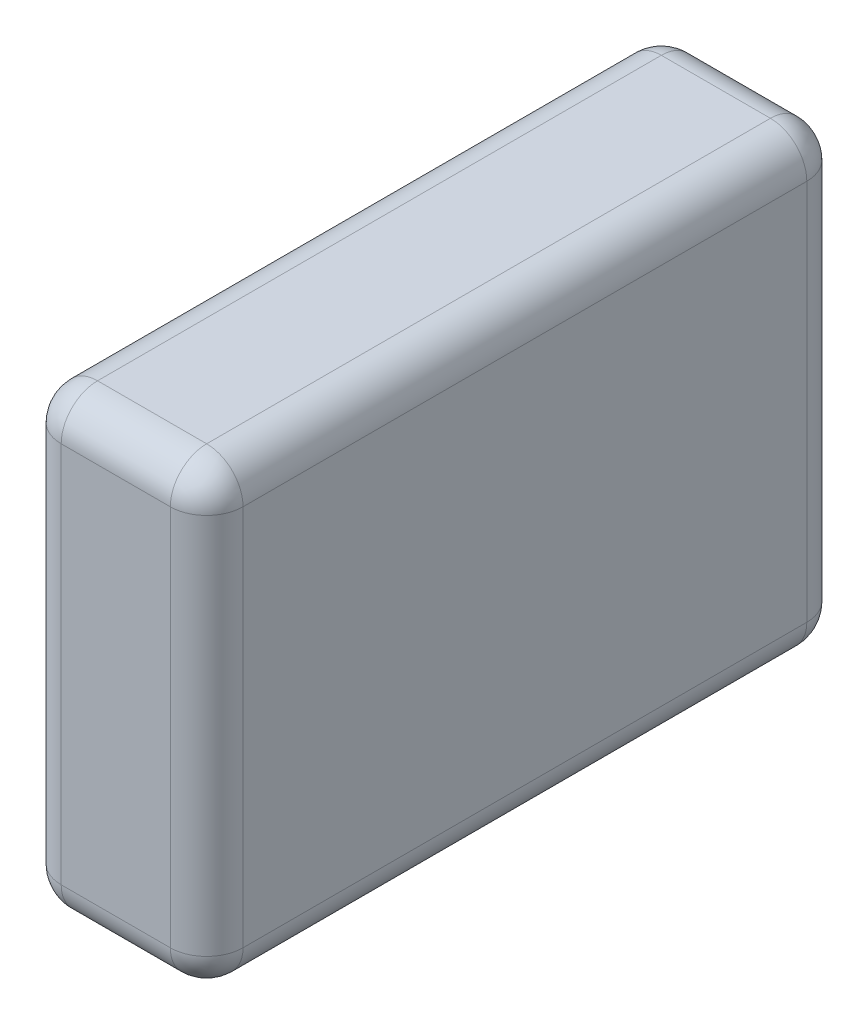
SolidWorks part; units mm, degrees
ref_plane "前视基准面" through (0, 0, 0) normal (0, 0, 1) x (1, 0, 0)
ref_plane "上视基准面" through (0, 0, 0) normal (0, 1, 0) x (1, 0, 0)
ref_plane "右视基准面" through (0, 0, 0) normal (1, 0, 0) x (0, 0, -1)
sketch "草图1" plane through (0, 0, 0) normal (1, 0, 0) x (0, 0, -1)
  line L1 (0, 0) -> (70, 0)
  line L2 (0, 0) -> (0, -50)
  line L3 (0, -50) -> (70, -50)
  line L4 (70, 0) -> (70, -50)
  dimension "D1" = 70
  dimension "D2" = 50
extrude "凸台-拉伸1" add sketch "草图1" along normal blind 20
fillet "圆角1" radius 4 4 edges at (0, -25, -70) (0, -50, -35) (0, 0, -35) (0, -25, 0)
fillet "圆角2" radius 4 4 edges at (20, -25, 0) (20, -25, -70) (20, -50, -35) (20, 0, -35)
fillet "圆角3" radius 4 12 edges at (18.8284, -1.1716, -68.8284) (1.1716, -1.1716, -68.8284) (18.8284, -1.1716, -1.1716) (1.1716, -1.1716, -1.1716) (18.8284, -48.8284, -1.1716) (1.1716, -48.8284, -1.1716) (18.8284, -48.8284, -68.8284) (1.1716, -48.8284, -68.8284) (10, 0, -70) (10, 0, 0) (10, -50, 0) (10, -50, -70)
